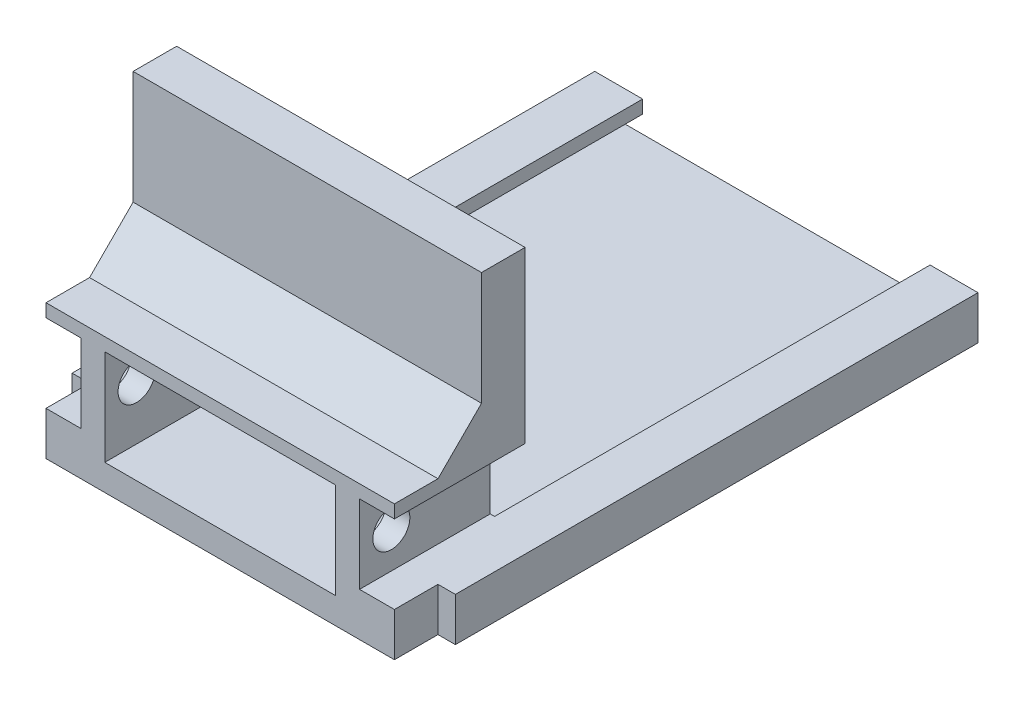
SolidWorks part; units mm, degrees
ref_plane "Front Plane" through (0, 0, 0) normal (0, 0, 1) x (1, 0, 0)
ref_plane "Top Plane" through (0, 0, 0) normal (0, 1, 0) x (1, 0, 0)
ref_plane "Right Plane" through (0, 0, 0) normal (1, 0, 0) x (0, 0, -1)
sketch "Sketch1" plane through (0, 0, 0) normal (0, 0, 1) x (1, 0, 0)
  line L1 (0, 0) -> (88, 0)
  line L2 (0, 0) -> (0, -10)
  line L3 (0, -10) -> (88, -10)
  line L4 (88, 0) -> (88, -10)
  line L5 (11, 0) -> (77, 0)
  line L6 (11, 0) -> (11, -3)
  line L7 (11, -3) -> (77, -3)
  line L8 (77, 0) -> (77, -3)
  line L9 (3, -3) -> (85, -3)
  line L10 (3, -3) -> (3, -7)
  line L11 (3, -7) -> (85, -7)
  line L12 (85, -3) -> (85, -7)
  dimension "D1" = 88
  dimension "D2" = 10
  dimension "D3" = 3
  dimension "D4" = 4
  dimension "D5" = 82
  dimension "D6" = 3
  dimension "D7" = 66
  dimension "D8" = 11
extrude "Boss-Extrude1" add sketch "Sketch1" along normal blind 100 contours L9 L12 L11 L10 L6 L1 L2 L3 L4 L8 region at (5.5, -0.8857, 0)
sketch "Sketch2" plane through (0, 0, 100) normal (0, 0, 1) x (1, 0, 0)
  line L0 (44, 57) -> (44, 0) construction
  line L1 (0, -10) -> (88, -10)
  line L2 (0, -10) -> (0, 0)
  line L3 (0, 0) -> (88, 0)
  line L4 (88, -10) -> (88, 0)
  line L5 (4, 0) -> (84, 0)
  line L6 (4, 0) -> (4, 57)
  line L7 (4, 57) -> (84, 57)
  line L8 (84, 0) -> (84, 57)
  line L9 (44, 0) -> (44, -10) construction
  line M11 (77, -3) -> (85, -3)
  line M12 (85, -3) -> (85, -7)
  line M13 (85, -7) -> (3, -7)
  line M14 (3, -7) -> (3, -3)
  line M15 (3, -3) -> (11, -3)
  line M16 (11, -3) -> (11, 0)
  line M17 (11, 0) -> (0, 0)
  line M18 (0, 0) -> (0, -10)
  line M19 (0, -10) -> (88, -10)
  line M20 (88, -10) -> (88, 0)
  line M21 (88, 0) -> (77, 0)
  line M22 (77, 0) -> (77, -3)
  dimension "D1" = 67
  dimension "D2" = 80
extrude "Boss-Extrude2" add sketch "Sketch2" along normal blind 20 contours L3 M16 M15 M14 M13 M12 M11 M22 | L3 L8 L7 L6 M17 | L3 M22 M11 M12 M13 M14 M15 M16 M17 M18 M19 M20 M21 region at (0.8857, -5, 100) region at (44, 28.5, 100) region at (44, -3.6825, 100)
sketch "Sketch4" plane through (0, 0, 120) normal (0, 0, 1) x (1, 0, 0)
  line L0 (4, 0) -> (4, 57) construction
  line L1 (4, -10) -> (84, -10)
  line L2 (4, -10) -> (4, 21)
  line L3 (4, 21) -> (84, 21)
  line L4 (84, -10) -> (84, 21)
  line L6 (84, 0) -> (84, 57) construction
  dimension "D1" = 31
extrude "Boss-Extrude3" add sketch "Sketch4" along normal blind 10
extrude "Boss-Extrude4" add sketch "Sketch4<2>" against normal up to surface (20 mm away) up to face at (44, 7.3333, 100)
sketch "Sketch4<2>" plane through (0, 0, 120) normal (0, 0, 1) x (1, 0, 0) same geometry as "Sketch4"
sketch "Sketch5" plane through (0, 0, 130) normal (0, 0, 1) x (1, 0, 0)
  line L0 (44, 21) -> (44, -10) construction
  line L1 (17.5, 18) -> (70.5, 18)
  line L2 (17.5, 18) -> (17.5, -4)
  line L3 (17.5, -4) -> (70.5, -4)
  line L4 (70.5, 18) -> (70.5, -4)
  line L5 (84, 21) -> (4, 21) construction
  line L6 (4, -10) -> (84, -10) construction
  line L7 (44, 18) -> (44, -4) construction
  line L8 (4, 21) -> (4, -10) construction
  line L9 (4, 18) -> (12, 18)
  line L10 (4, 18) -> (4, 0)
  line L11 (4, 0) -> (12, 0)
  line L12 (12, 18) -> (12, 0)
  line L13 (84, -10) -> (84, 21) construction
  line L14 (84, 18) -> (76, 18)
  line L15 (84, 18) -> (84, 0)
  line L16 (84, 0) -> (76, 0)
  line L17 (76, 18) -> (76, 0)
  dimension "D1" = 6
  dimension "D2" = 22
  dimension "D3" = 53
  dimension "D4" = 18
  dimension "D5" = 18
  dimension "D6" = 5.5
  dimension "D7" = 5.5
extrude "Cut-Extrude1" cut sketch "Sketch5" against normal up to surface (30 mm away) up to face at (44, 7.3333, 100)
sketch "Sketch6" plane through (4, 0, 0) normal (-1, 0, 0) x (0, 0, 1)
  line L0 (120, 57) -> (100, 57) construction
  line L1 (110, 57) -> (120, 57)
  line L2 (110, 57) -> (110, 21)
  line L3 (110, 21) -> (120, 21)
  line L4 (120, 57) -> (120, 21)
extrude "Cut-Extrude2" cut sketch "Sketch6" against normal up to surface (80 mm away) up to face at (84, 32, 116.6667)
sketch "Sketch7" plane through (76, 0, 0) normal (1, 0, 0) x (0, 0, -1)
  line L0 (-100, 8.5) -> (-122.7, 8.5)
  line L1 (-100, 0) -> (-100, 18) construction
  line L3 (-100, 18) -> (-130, 18) construction
  circle A0 centre (-122.7, 8.5) radius 4.25
  dimension "D3" = 8.5
  dimension "D1" = 22.7
  dimension "D2" = 9.5
extrude "Cut-Extrude3" cut sketch "Sketch7" against normal through all contours A0
chamfer "Chamfer1" distance 10 angle 45 1 edges at (44, 21, 110)
